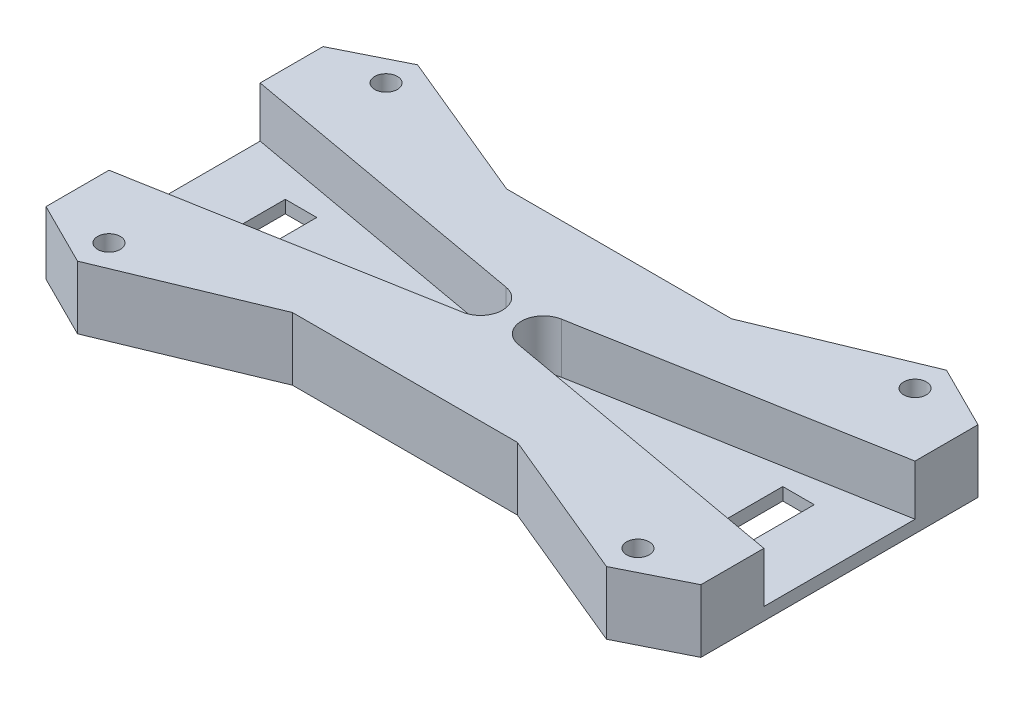
SolidWorks part; units mm, degrees
ref_plane "Front Plane" through (0, 0, 0) normal (0, 0, 1) x (1, 0, 0)
ref_plane "Top Plane" through (0, 0, 0) normal (0, 1, 0) x (1, 0, 0)
ref_plane "Right Plane" through (0, 0, 0) normal (1, 0, 0) x (0, 0, -1)
sketch "Sketch1" plane through (0, 0, 0) normal (0, 1, 0) x (1, 0, 0)
  line L0 (0, 0) -> (51.8933, 0) construction
  line L1 (0, 0) -> (0, 53.9) construction
  line L2 (-72.403, 22) -> (98.2779, 22) construction
  line L3 (-42, -22) -> (42, -22) construction
  line L4 (-42, -22) -> (-42, 22) construction
  line L5 (-42, 22) -> (42, 22) construction
  line L6 (42, -22) -> (42, 22) construction
  line L7 (-42, -22) -> (42, 22) construction
  line L8 (-42, 22) -> (42, -22) construction
  line L9 (-52, -27) -> (52, -27)
  line L10 (-52, -27) -> (-52, 27)
  line L11 (-52, 27) -> (52, 27)
  line L12 (52, -27) -> (52, 27)
  line L13 (-52, -27) -> (52, 27) construction
  line L14 (-52, 27) -> (52, -27) construction
  line L15 (42, 80.7884) -> (42, -69.174) construction
  line L16 (3.9562, 37.7583) -> (70.6061, 10.1509) construction
  line L17 (80.0438, 37.7583) -> (13.3939, 10.1509) construction
  line L18 (52, 22) -> (42, 27)
  line L19 (42, 27) -> (17.8579, 17)
  line L20 (17.8579, 17) -> (0, 17)
  line L21 (52, 12) -> (4.3811, 3.4448)
  line L22 (52, -12) -> (4.3811, -3.4448)
  line L23 (-52, -12) -> (-4.3811, -3.4448)
  line L24 (-52, 12) -> (-4.3811, 3.4448)
  line L25 (-52, 22) -> (-42, 27)
  line L26 (-42, 27) -> (-17.8579, 17)
  line L27 (-17.8579, 17) -> (0, 17)
  line L28 (52, -22) -> (42, -27)
  line L29 (42, -27) -> (17.8579, -17)
  line L30 (17.8579, -17) -> (0, -17)
  line L31 (-17.8579, -17) -> (0, -17)
  line L32 (-42, -27) -> (-17.8579, -17)
  line L33 (-52, -22) -> (-42, -27)
  line L34 (45.1305, 20.4348) -> (47.1305, 24.4348)
  line L35 (40.6606, 18.7664) -> (31.3915, 22.6058)
  line L36 (-45.1305, 20.4348) -> (-47.1305, 24.4348)
  line L37 (-40.6606, 18.7664) -> (-31.3915, 22.6058)
  line L38 (45.1305, -20.4348) -> (47.1305, -24.4348)
  line L39 (40.6606, -18.7664) -> (31.3915, -22.6058)
  line L40 (-40.6606, -18.7664) -> (-31.3915, -22.6058)
  line L41 (-45.1305, -20.4348) -> (-47.1305, -24.4348)
  line L42 (42, 6) -> (37, 6)
  line L43 (37, 6) -> (37, -6)
  line L44 (37, -6) -> (42, -6)
  line L45 (42, -6) -> (42, 6)
  line L46 (-37, -6) -> (-42, -6)
  line L47 (-37, 6) -> (-37, -6)
  line L48 (-42, 6) -> (-37, 6)
  line L49 (-42, -6) -> (-42, 6)
  circle A0 centre (42, 22) radius 1.8
  circle A1 centre (-42, 22) radius 1.8
  circle A2 centre (-42, -22) radius 1.8
  circle A3 centre (42, -22) radius 1.8
  arc A4 (4.3811, 3.4448) -> (4.3811, -3.4448) centre (5, 0) ccw
  arc A5 (-4.3811, 3.4448) -> (-4.3811, -3.4448) centre (-5, 0) cw
  arc A6 (45.1305, 20.4348) -> (40.6606, 18.7664) centre (42, 22) cw
  arc A7 (-45.1305, 20.4348) -> (-40.6606, 18.7664) centre (-42, 22) ccw
  arc A8 (45.1305, -20.4348) -> (40.6606, -18.7664) centre (42, -22) ccw
  arc A9 (-45.1305, -20.4348) -> (-40.6606, -18.7664) centre (-42, -22) cw
  point P4 (0, 0)
  point P12 (0, 0)
  point P38 (1.5, 0)
  dimension "D5" = 3.6
  dimension "D8" = 1.5
  dimension "D10" = 3.5
  dimension "D11" = 3.5
  dimension "D1" = 84
  dimension "D2" = 44
  dimension "D3" = 10
  dimension "D4" = 5
  dimension "D6" = 22.5
  dimension "D7" = 17
  dimension "D9" = 24
  dimension "D12" = 5
  dimension "D13" = 12
extrude "Boss-Extrude1" add sketch "Sketch1" along normal blind 10 contours L41 A9 L40 L32 L31 L30 L29 L39 A8 L38 L28 L12 L22 A4 L21 L18 L34 A6 L35 L19 L20 L27 L26 L37 A7 L36 L25 L10 L24 A5 L23 L33 | L36 A7 L37 L26 L25 A1 | A9 L41 L33 L32 L40 A2 | A6 L34 L18 L19 L35 A0 | L38 A8 L39 L29 L28 A3 region at (-40.2207, 0, 22.7842) region at (0, 0, 0) region at (40.2207, 0, 22.7842) region at (-40.2207, 0, -22.7842) region at (40.2207, 0, -22.7842)
extrude "Boss-Extrude2" add sketch "Sketch1<3>" along normal blind 2 contours L21 A4 L22 L12 | A5 L24 L10 L23 region at (-31.3497, 0, 0) region at (31.3497, 0, 0)
sketch "Sketch1<3>" plane through (0, 0, 0) normal (0, 1, 0) x (1, 0, 0) same geometry as "Sketch1"
